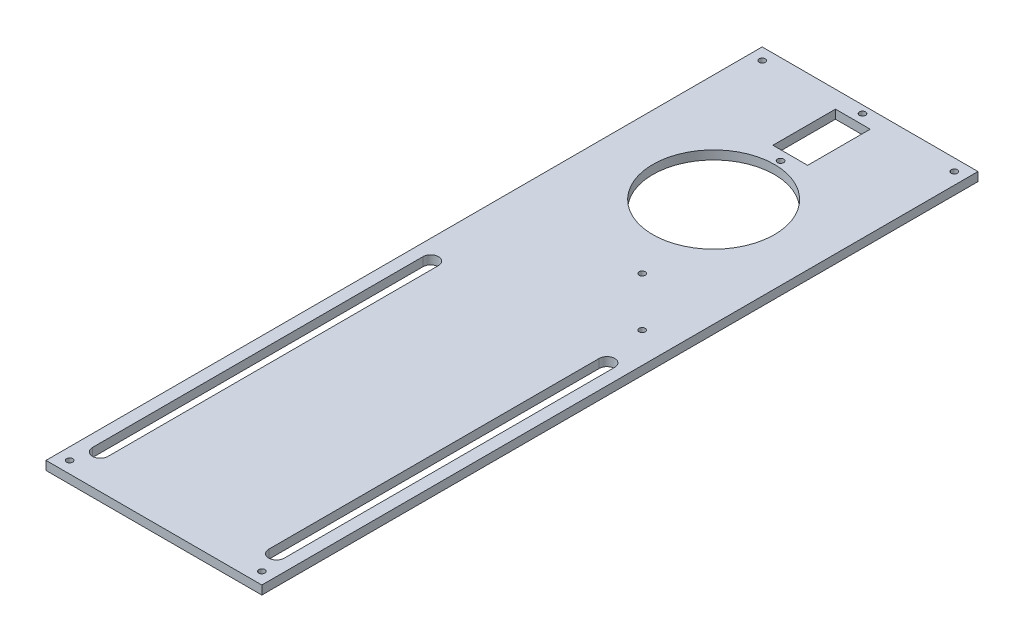
SolidWorks part; units mm, degrees
material "Brass"
ref_plane "Front Plane" through (0, 0, 0) normal (0, 0, 1) x (1, 0, 0)
ref_plane "Top Plane" through (0, 0, 0) normal (0, 1, 0) x (1, 0, 0)
ref_plane "Right Plane" through (0, 0, 0) normal (1, 0, 0) x (0, 0, -1)
sketch "Sketch2" plane through (0, 0, 0) normal (0, 0, 1) x (1, 0, 0)
  line L0 (-44.45, 0) -> (-44.45, -3.2004)
  line L1 (0, 0) -> (0, -3.2004) construction
  line L2 (-44.45, -3.2004) -> (34.3945, -3.2004)
  line L3 (34.3945, 0) -> (34.3945, -3.2004)
  line L4 (-44.45, 0) -> (34.3945, 0)
  dimension "D1" = 78.8445
  dimension "D2" = 3.2004
extrude "Boss-Extrude1" add sketch "Sketch2" along normal blind 261.62 contours L4 L3 L2 L0
sketch "Sketch3" plane through (0, -3.2004, 0) normal (0, -1, 0) x (1, 0, 0)
  line L0 (-44.45, 57.15) -> (34.3945, 57.15) construction
  line L1 (30.0765, 261.62) -> (30.0765, 257.302) construction
  line L2 (30.0765, 257.302) -> (34.3945, 257.302) construction
  line L3 (-44.45, 261.62) -> (34.3945, 261.62) construction
  line L4 (-5.0278, 57.15) -> (-5.0278, 0) construction
  line L5 (-44.45, 0) -> (34.3945, 0) construction
  line L6 (-40.0535, 128.3174) -> (-34.3859, 128.3174) construction
  line L7 (-40.0535, 128.3174) -> (-40.0535, 249.024)
  line L8 (-40.0535, 249.024) -> (-34.3859, 249.024) construction
  line L9 (-34.3859, 128.3174) -> (-34.3859, 249.024)
  line L10 (-37.2197, 261.62) -> (-37.2197, 251.8579) construction
  line L11 (-40.0535, 188.6707) -> (-44.45, 188.6707) construction
  line L12 (24.3303, 128.3174) -> (29.998, 128.3174) construction
  line L13 (24.3303, 128.3174) -> (24.3303, 249.024)
  line L14 (24.3303, 249.024) -> (29.998, 249.024) construction
  line L15 (29.998, 128.3174) -> (29.998, 249.024)
  line L16 (27.1642, 261.62) -> (27.1642, 251.8579) construction
  line L17 (34.3945, 188.6707) -> (29.998, 188.6707) construction
  line L18 (34.3945, 261.62) -> (34.3945, 0) construction
  line L19 (-44.45, 4.318) -> (-40.132, 4.318) construction
  line L20 (34.3945, 261.62) -> (34.3945, 0) construction
  line L21 (-44.45, 261.62) -> (-44.45, 0) construction
  line L22 (-44.45, 261.62) -> (-44.45, 0) construction
  line L23 (-40.132, 261.62) -> (-40.132, 257.302) construction
  line L24 (-44.45, 257.302) -> (-40.132, 257.302) construction
  line L25 (-44.45, 261.62) -> (34.3945, 261.62) construction
  line L26 (-40.132, 4.318) -> (-40.132, 0) construction
  line L27 (-44.45, 0) -> (34.3945, 0) construction
  line L28 (34.3945, 4.318) -> (30.0765, 4.318) construction
  line L29 (30.0765, 0) -> (30.0765, 4.318) construction
  line L30 (-11.3778, 29.1559) -> (-11.3778, 6.2959)
  line L31 (1.3222, 29.1559) -> (1.3222, 6.2959)
  line L32 (-11.3778, 6.2959) -> (1.3222, 6.2959)
  line L33 (-11.3778, 29.1559) -> (1.3222, 29.1559)
  line L34 (23.2109, 111.5162) -> (34.3945, 111.5162) construction
  line L35 (23.2109, 261.62) -> (23.2109, 111.5162) construction
  line L36 (5.3132, 93.6185) -> (23.2109, 111.5162) construction
  line L37 (5.3132, 93.6185) -> (34.3945, 93.6185) construction
  circle A0 centre (-5.0278, 57.15) radius 22.225
  arc A1 (-40.0535, 249.024) -> (-34.3859, 249.024) centre (-37.2197, 249.024) cw
  arc A2 (-34.3859, 128.3174) -> (-40.0535, 128.3174) centre (-37.2197, 128.3174) cw
  arc A3 (24.3303, 249.024) -> (29.998, 249.024) centre (27.1642, 249.024) cw
  arc A4 (29.998, 128.3174) -> (24.3303, 128.3174) centre (27.1642, 128.3174) cw
  circle A5 centre (-40.132, 257.302) radius 1.1303
  circle A6 centre (30.0765, 257.302) radius 1.1303
  circle A7 centre (-40.132, 4.318) radius 1.1303
  circle A8 centre (30.0765, 4.318) radius 1.1303
  circle A9 centre (-5.0278, 32.6865) radius 1.1303
  circle A10 centre (-5.0278, 2.7653) radius 1.1303
  circle A11 centre (5.3132, 93.6185) radius 1.1303
  circle A12 centre (23.2109, 111.5162) radius 1.1303
  point P53 (-5.0278, 29.1559)
  point P58 (-5.0278, 29.1559)
  point P67 (-5.0278, 6.2959)
  dimension "D1" = 44.45
  dimension "D11" = 2.2606
  dimension "D15" = 2.2606
  dimension "D16" = 2.7653
  dimension "D18" = 3.5306
  dimension "D19" = 2.2606
  dimension "D2" = 57.15
  dimension "D3" = 120.7066
  dimension "D4" = 5.6676
  dimension "D5" = 9.7621
  dimension "D6" = 4.3965
  dimension "D7" = 120.7066
  dimension "D8" = 5.6676
  dimension "D9" = 9.7621
  dimension "D10" = 4.3965
  dimension "D12" = 4.318
  dimension "D13" = 22.86
  dimension "D14" = 12.7
  dimension "D17" = 3.5306
  dimension "D20" = 150.1038
  dimension "D21" = 11.1836
  dimension "D22" = 25.3111
  dimension "D23" = 29.0813
extrude "Cut-Extrude1" cut sketch "Sketch3" against normal through all
